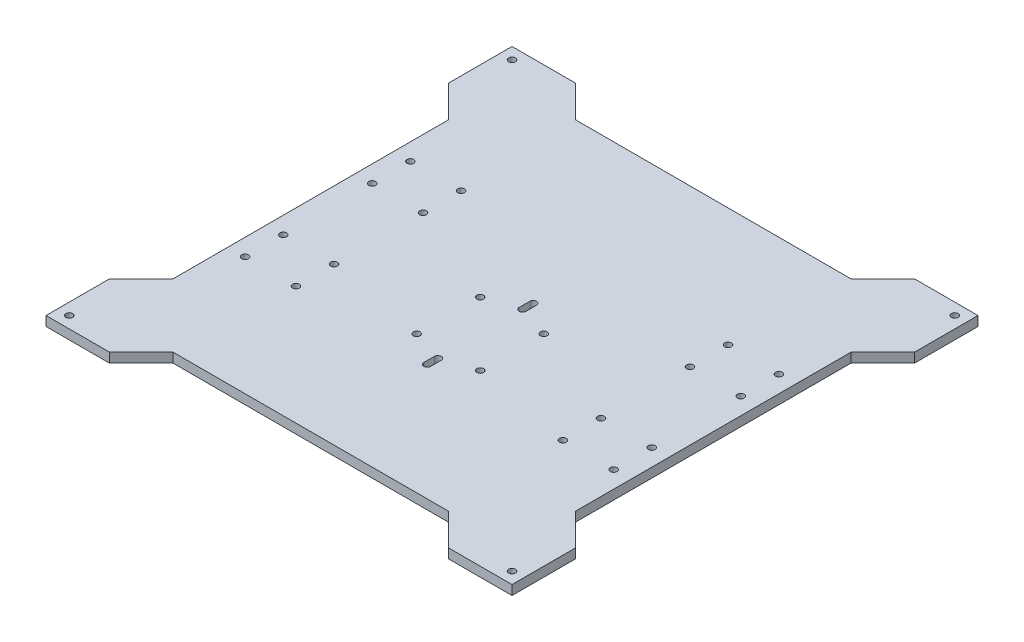
SolidWorks part; units mm, degrees
ref_plane "Front Plane" through (0, 0, 0) normal (0, 0, 1) x (1, 0, 0)
ref_plane "Top Plane" through (0, 0, 0) normal (0, 1, 0) x (1, 0, 0)
ref_plane "Right Plane" through (0, 0, 0) normal (1, 0, 0) x (0, 0, -1)
sketch "Sketch1" plane through (0, 0, 0) normal (0, 1, 0) x (1, 0, 0)
  line L1 (-110, 110) -> (110, 110)
  line L2 (-110, 110) -> (-110, -110)
  line L3 (-110, -110) -> (110, -110)
  line L4 (110, 110) -> (110, -110)
  line L5 (-110, 110) -> (110, -110) construction
  line L6 (-110, -110) -> (110, 110) construction
  point P0 (0, 0)
  dimension "D1" = 220
  dimension "D2" = 220
extrude "Square" add sketch "Sketch1" along normal blind 4.5
sketch "Sketch2" plane through (0, 4.5, 0) normal (0, 1, 0) x (1, 0, 0)
  line L0 (0, 110) -> (0, -110) construction
  line L1 (110, 110) -> (-110, 110) construction
  line L2 (-110, -110) -> (110, -110) construction
  line L3 (-110, 0) -> (110, 0) construction
  line L4 (-110, 110) -> (-110, -110) construction
  line L5 (110, -110) -> (110, 110) construction
  line L6 (75, 110) -> (75, -110) construction
  line L7 (75, 30) -> (0, 30) construction
  line L8 (75, -30) -> (0, -30) construction
  circle A0 centre (87, 39) radius 1.6
  circle A1 centre (87, 21) radius 1.6
  circle A2 centre (63, 21) radius 1.6
  circle A3 centre (63, 39) radius 1.6
  circle A4 centre (-63, 39) radius 1.6
  circle A5 centre (-63, 21) radius 1.6
  circle A6 centre (-87, 21) radius 1.6
  circle A7 centre (-87, 39) radius 1.6
  circle A8 centre (-87, 21) radius 1.6
  circle A9 centre (-87, 39) radius 1.6
  circle A10 centre (-63, 39) radius 1.6
  circle A11 centre (-63, 21) radius 1.6
  circle A12 centre (63, 21) radius 1.6
  circle A13 centre (63, 39) radius 1.6
  circle A14 centre (87, 39) radius 1.6
  circle A15 centre (87, 21) radius 1.6
  circle A16 centre (87, -21) radius 1.6
  circle A17 centre (87, -39) radius 1.6
  circle A18 centre (63, -39) radius 1.6
  circle A19 centre (63, -21) radius 1.6
  circle A20 centre (-63, -21) radius 1.6
  circle A21 centre (-63, -39) radius 1.6
  circle A22 centre (-87, -39) radius 1.6
  circle A23 centre (-87, -21) radius 1.6
  circle A24 centre (-87, -39) radius 1.6
  circle A25 centre (-87, -21) radius 1.6
  circle A26 centre (-63, -21) radius 1.6
  circle A27 centre (-63, -39) radius 1.6
  circle A28 centre (63, -39) radius 1.6
  circle A29 centre (63, -21) radius 1.6
  circle A30 centre (87, -21) radius 1.6
  circle A31 centre (87, -39) radius 1.6
  dimension "D6" = 3.2
  dimension "D7" = 3.2
  dimension "D1" = 75
  dimension "D2" = 30
  dimension "D3" = 18
  dimension "D5" = 12
extrude "LM8UU-Holders" cut sketch "Sketch2" against normal through all contours A7 | A6 | A5 | A4 | A20 | A21 | A22 | A23 | A19 | A18 | A17 | A16 | A1 | A0 | A3 | A2 region at (87, 4.5, -39) region at (87, 4.5, -21) region at (63, 4.5, -21) region at (63, 4.5, -39) region at (-63, 4.5, -39) region at (-63, 4.5, -21) region at (-87, 4.5, -21) region at (-87, 4.5, -39) region at (87, 4.5, 21) region at (87, 4.5, 39) region at (63, 4.5, 39) region at (63, 4.5, 21) region at (-63, 4.5, 21) region at (-63, 4.5, 39) region at (-87, 4.5, 39) region at (-87, 4.5, 21)
sketch "Sketch3" plane through (0, 4.5, 0) normal (0, 1, 0) x (1, 0, 0)
  line L0 (0, -110) -> (0, 110) construction
  line L1 (-110, -110) -> (110, -110) construction
  line L2 (110, 110) -> (-110, 110) construction
  line L3 (110, -15) -> (-110, -15) construction
  line L6 (15, -30) -> (-15, -30) construction
  line L7 (15, 0) -> (-15, 0) construction
  line L8 (110, -110) -> (110, 110) construction
  line L9 (-110, 110) -> (-110, -110) construction
  line L10 (110, 0) -> (-110, 0) construction
  circle A0 centre (-15, -30) radius 1.6
  circle A1 centre (15, -30) radius 1.6
  circle A2 centre (15, 0) radius 1.6
  circle A3 centre (-15, 0) radius 1.6
  point P16 (0, -30)
  dimension "D1" = 3.2
  dimension "D2" = 15
  dimension "D3" = 15
  dimension "D5" = 15
extrude "DefaultBelt" cut sketch "Sketch3" against normal through all
sketch "Sketch4" plane through (0, 4.5, 0) normal (0, 1, 0) x (1, 0, 0)
  line L0 (0, 110) -> (0, -110) construction
  line L1 (110, 110) -> (-110, 110) construction
  line L2 (-110, -110) -> (110, -110) construction
  line L3 (-15, -1.6) -> (-15, -28.4) construction
  line L4 (15, -28.4) -> (15, -1.6) construction
  line L5 (15, -15) -> (-15, -15) construction
  line L6 (0, 10) -> (0, 5) construction
  line L7 (1.6, 10) -> (1.6, 5)
  line L8 (-1.6, 10) -> (-1.6, 5)
  line L9 (0, -40) -> (0, -35) construction
  line L10 (1.6, -40) -> (1.6, -35)
  line L11 (-1.6, -40) -> (-1.6, -35)
  arc A0 (1.6, -40) -> (-1.6, -40) centre (0, -40) cw
  arc A1 (1.6, 10) -> (-1.6, 10) centre (0, 10) ccw
  arc A2 (-1.6, 5) -> (1.6, 5) centre (0, 5) ccw
  arc A3 (-1.6, -35) -> (1.6, -35) centre (0, -35) cw
  circle A4 centre (-15, 0) radius 1.6 construction
  circle A5 centre (-15, -30) radius 1.6 construction
  circle A6 centre (15, -30) radius 1.6 construction
  circle A7 centre (15, 0) radius 1.6 construction
  point P16 (0, 7.5)
  point P22 (0, -37.5)
  dimension "D3" = 3.2
  dimension "D1" = 20
  dimension "D2" = 25
extrude "BeltOptions" cut sketch "Sketch4" against normal through all
sketch "Sketch5" plane through (0, 4.5, 0) normal (0, 1, 0) x (1, 0, 0)
  line L0 (-110, 0) -> (110, 0) construction
  line L1 (-110, 110) -> (-110, -110) construction
  line L2 (110, -110) -> (110, 110) construction
  line L3 (0, 110) -> (0, -110) construction
  line L4 (110, 110) -> (-110, 110) construction
  line L5 (-110, 110) -> (-110, 80)
  line L6 (-110, 80) -> (-95, 65)
  line L7 (-95, 65) -> (-95, -65)
  line L8 (0, 0) -> (-110, 110) construction
  line L9 (-65, 95) -> (65, 95)
  line L10 (-80, 110) -> (-65, 95)
  line L11 (-110, 110) -> (-80, 110)
  line L12 (-95, 65) -> (-95, -65)
  line L13 (0, 0) -> (110, 110) construction
  line L14 (95, 65) -> (95, -65)
  line L15 (110, 110) -> (80, 110)
  line L16 (80, 110) -> (65, 95)
  line L17 (95, 65) -> (95, -65)
  line L18 (110, 80) -> (95, 65)
  line L19 (110, 110) -> (110, 80)
  line L20 (0, 0) -> (110, -110) construction
  line L21 (0, 0) -> (-110, -110) construction
  line L22 (110, -110) -> (110, -80)
  line L23 (110, -80) -> (95, -65)
  line L24 (80, -110) -> (65, -95)
  line L25 (110, -110) -> (80, -110)
  line L26 (-110, -110) -> (-80, -110)
  line L27 (-80, -110) -> (-65, -95)
  line L28 (-65, -95) -> (65, -95)
  line L29 (-110, -80) -> (-95, -65)
  line L30 (-110, -110) -> (-110, -80)
  point P24 (0, 95)
  point P32 (95, 0)
  point P35 (-95, 0)
  point P36 (0, -95)
  circle M16 centre (15, -30) radius 1.6
  circle M18 centre (63, 39) radius 1.6
  circle M20 centre (87, 21) radius 1.6
  circle M22 centre (87, -39) radius 1.6
  circle M23 centre (63, -39) radius 1.6
  circle M24 centre (63, -21) radius 1.6
  circle M25 centre (-87, -21) radius 1.6
  circle M26 centre (-87, -39) radius 1.6
  circle M27 centre (-63, -39) radius 1.6
  circle M28 centre (-63, -21) radius 1.6
  circle M29 centre (-63, 39) radius 1.6
  circle M30 centre (-63, 21) radius 1.6
  circle M31 centre (-87, 21) radius 1.6
  circle M32 centre (-87, 39) radius 1.6
  line M33 (110, -110) -> (110, 110)
  line M34 (110, 110) -> (-110, 110)
  line M35 (-110, 110) -> (-110, -110)
  line M36 (-110, -110) -> (110, -110)
  dimension "D1" = 15
  dimension "D2" = 30
  dimension "D3" = 45
  dimension "D4" = 45
extrude "Shaping" cut sketch "Sketch5" against normal blind 10 flip side to cut contours L29 L27 L28 L24 L23 L14 L18 L16 L9 L10 L6 L7 M35 M36 M33 M34 M16 M18 M20 M22 M24 M26 M28 M30 M32 M31 M29 M27 M25 M23 region at (0.0451, 4.5, -0.014)
sketch "Sketch6" plane through (0, 4.5, 0) normal (0, 1, 0) x (1, 0, 0)
  line L0 (-110, 110) -> (110, -110) construction
  line L1 (-110, -110) -> (110, 110) construction
  line L2 (110, 80) -> (110, 110) construction
  line L3 (0, 95) -> (0, -95) construction
  line L4 (-65, 95) -> (65, 95) construction
  line L5 (-65, -95) -> (65, -95) construction
  line L6 (-95, 0) -> (95, 0) construction
  line L7 (-95, 65) -> (-95, -65) construction
  line L8 (95, 65) -> (95, -65) construction
  circle A0 centre (-104.5, 104.5) radius 1.6
  circle A1 centre (104.5, 104.5) radius 1.6
  circle A2 centre (104.5, -104.5) radius 1.6
  circle A3 centre (-104.5, -104.5) radius 1.6
  dimension "D2" = 3.2
  dimension "D1" = 45
  dimension "D3" = 104.5
extrude "Cut-Extrude5" cut sketch "Sketch6" against normal through all
equation "\"X-ROD-SPACING\"=45"
equation "\"Y-ROD-SPACING\"=75"
equation "\"Z-ROD-SPACING\"=17.5"
equation "\"Y-BED-OFFSET\"=2"
equation "\"Y-BED-ROD-INSET\"=3.5"
equation "\"T-SLOT-NUT-FILLET-RADIUS\"=0.25"
equation "\"T-SLOT-SCREW-SHAFT-RADIUS\"=1.75"
equation "\"T-SLOT-SCREW-SHAFT-CUTOUT-LENGTH\"=10.5"
equation "\"T-SLOT-NUT-DEPTH\"=4.2"
equation "\"T-SLOT-NUT-WIDTH\"=3"
equation "\"T-SLOT-NUT-END-DISTANCE\"=8"
equation "\"ACRYLIC-THICKNESS\"=10"
equation "\"ACRYLIC-THICKNESS2\"=4.5"
equation "\"ACRYLIC-TAB-CUTOUT-SIZE\"=\"ACRYLIC-THICKNESS\"+\"ACRYLIC-TAB-TOLERANCE\"*2"
equation "\"ACRYLIC-TAB-WIDTH\"=\"ACRYLIC-THICKNESS\""
equation "\"ACRYLIC-M3-HOLE\"=3.2"
equation "\"SMOOTHROD-CAP-SCREW-DISTANCE\"=20"
equation "\"FRAME-WIDTH-INNER\"=370"
equation "\"NEMA17-HOLE-SPACING\"=31"
equation "\"NEMA17-CENTRAL-CUTOUT\"=22.5"
equation "\"Z-BRACKET-REACH\"=55"
equation "\"TOP-BRACKET-SPACING\"=40"
equation "\"SMOOTHROD-X-LENGTH\"=350"
equation "\"SMOOTHROD-Y-LENGTH\"=350"
equation "\"SMOOTHROD-Z-LENGTH\"=350"
equation "\"SMOOTHROD-TIGHTENING-HEADROOM\"=1"
equation "\"LEADSCREW-Z-LENGTH\"=300"
equation "\"SCREW-LENGTH-FRAME\"=\"ACRYLIC-THICKNESS\" + 10"
equation "\"SCREW-HEAD-RADIUS\"=6"
equation "\"PRINTED-X-SMOOTHROD-DIAMETER\"=8.2"
equation "\"PRINTED-X-SMOOTHROD-CUTOUT\"=10"
equation "\"PRINTED-X-BASE-HEIGHT\"=10"
equation "\"PRINTED-LM8UU-CUTOUT-SIZE\"=16"
equation "\"PRINTED-LM8UU-CUTOUT-LENGTH\"=24.5"
equation "\"PRINTED-X-IDLER-HEIGHT\"=16"
equation "\"PSU-MOUNTING-WIDTH\"=95"
equation "\"PSU-MOUNTING-HEIGHT\"=177"
equation "\"Y-BELT-TO-ROD-DISTANCE\"=20"
equation "\"D6@Sketch2\"=\"ACRYLIC-M3-HOLE\""
equation "\"D7@Sketch2\"=\"ACRYLIC-M3-HOLE\""
equation "\"D1@Sketch2\"=\"Y-ROD-SPACING\""
equation "\"D1@Sketch3\"=\"ACRYLIC-M3-HOLE\""
equation "\"D3@Sketch4\"=\"ACRYLIC-M3-HOLE\""
equation "\"D2@Sketch6\"=\"ACRYLIC-M3-HOLE\""
